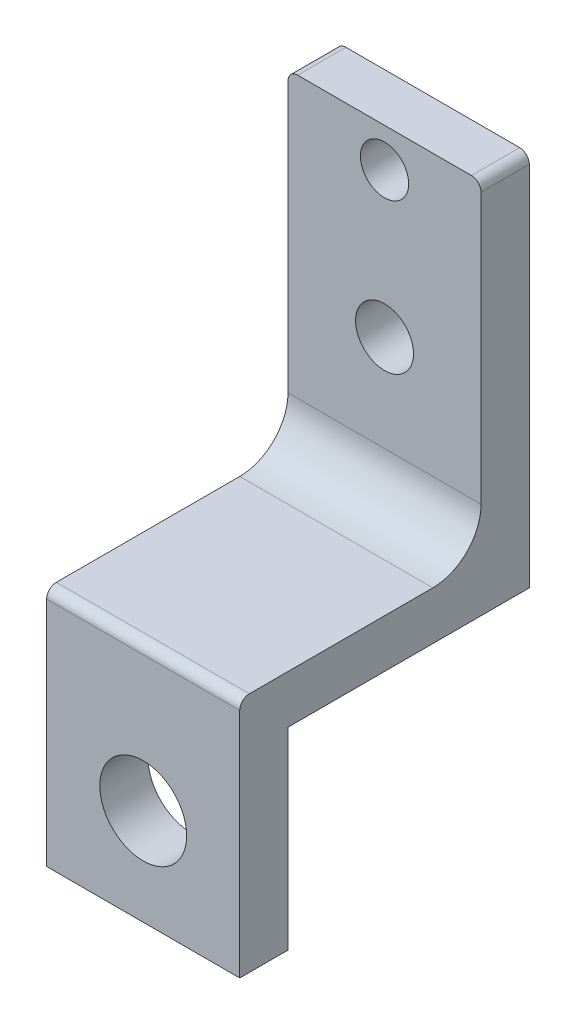
SolidWorks part; units mm, degrees
material "6061 Alloy"
ref_plane "前视基准面" through (0, 0, 0) normal (0, 0, 1) x (1, 0, 0)
ref_plane "上视基准面" through (0, 0, 0) normal (0, 1, 0) x (1, 0, 0)
ref_plane "右视基准面" through (0, 0, 0) normal (1, 0, 0) x (0, 0, -1)
other "Configuration Table"
sketch "Sketch1" plane through (0, 0, 0) normal (0, 0, 1) x (1, 0, 0)
  line L0 (0, 0) -> (0, 30) construction
  line L2 (-10, 10) -> (-10, -10)
  line L3 (-10, -10) -> (10, -10)
  line L4 (10, 10) -> (10, -10)
  line L5 (-10, 10) -> (10, -10) construction
  line L6 (-10, -10) -> (10, 10) construction
  line L7 (0, 30) -> (0, 45) construction
  line L8 (0, 45) -> (0, 49) construction
  line L9 (10, 49) -> (-10, 49)
  line L10 (-10, 49) -> (-10, 10)
  line L11 (10, 49) -> (10, 10)
  circle A0 centre (0, 0) radius 4.5
  circle A1 centre (0, 30) radius 3 construction
  circle A2 centre (0, 45) radius 2.5 construction
  dimension "D1" = 20
  dimension "D3" = 9
  dimension "D5" = 6
  dimension "D7" = 5
  dimension "D2" = 20
  dimension "D4" = 30
  dimension "D6" = 15
  dimension "D8" = 4
extrude "Boss-Extrude1" add sketch "Sketch1" along normal blind 5
sketch "Sketch2" plane through (0, 0, 0) normal (0, 0, -1) x (-1, 0, 0)
  line L1 (-10, -10) -> (10, -10) construction
  line L2 (-10, -10) -> (-10, 10) construction
  line L3 (-10, 10) -> (10, 10) construction
  line L4 (10, -10) -> (10, 10) construction
  line L5 (-10, -10) -> (10, 10) construction
  line L6 (-10, 10) -> (10, -10) construction
  line L7 (-10, 49) -> (10, 49)
  line L8 (-10, 49) -> (-10, 10)
  line L9 (-10, 10) -> (10, 10)
  line L10 (10, 49) -> (10, 10)
  point P0 (0, 0)
  dimension "D1" = 20
  dimension "D2" = 20
extrude "Boss-Extrude2" add sketch "Sketch2" along normal blind 25
sketch "Sketch3" plane through (10, 0, 0) normal (1, 0, 0) x (0, 0, -1)
  line L0 (0, 10) -> (0, 15) construction
  line L1 (0, 15) -> (-5, 15)
  line L2 (-5, -10) -> (-5, 49) construction
  line L3 (-5, 15) -> (-5, 49)
  line L4 (-5, 49) -> (20, 49)
  line L5 (-5, 49) -> (25, 49) construction
  line L6 (20, 49) -> (20, 15)
  line L7 (20, 15) -> (0, 15)
  dimension "D1" = 5
extrude "Cut-Extrude1" cut sketch "Sketch3" against normal blind 30
sketch "Sketch4" plane through (0, 0, -20) normal (0, 0, 1) x (1, 0, 0)
  circle A0 centre (0, 45) radius 2.5
  circle A1 centre (0, 30) radius 3
extrude "Cut-Extrude2" cut sketch "Sketch4" against normal blind 30
fillet "Fillet1" radius 5 1 edges at (0, 15, -20)
fillet "Fillet2" radius 1 3 edges at (0, 15, 5) (-10, 49, -22.5) (10, 49, -22.5)
mirror "Mirror1" [suppressed] of bodies 109
delete or keep bodies "Body-Delete/Keep 1" [suppressed] type delete bodies bodies 109
